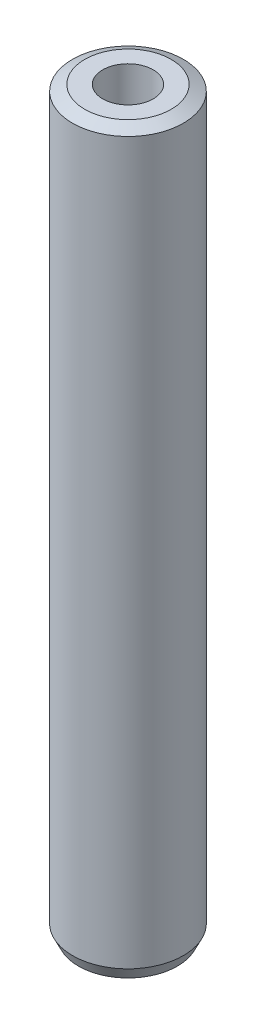
SolidWorks part; units mm, degrees
ref_plane "Front Plane" through (0, 0, 0) normal (0, 0, 1) x (1, 0, 0)
ref_plane "Top Plane" through (0, 0, 0) normal (0, 1, 0) x (1, 0, 0)
ref_plane "Right Plane" through (0, 0, 0) normal (1, 0, 0) x (0, 0, -1)
sketch "Sketch1" plane through (0, 0, 0) normal (0, 1, 0) x (1, 0, 0)
  circle A0 centre (0, 0) radius 45
  dimension "SHAFT_OD" = 90
extrude "Boss-Extrude1" add sketch "Sketch1" along normal blind 600
sketch "Sketch2" plane through (0, 0, 0) normal (0, 1, 0) x (1, 0, 0)
  circle A0 centre (0, 0) radius 20.4917
  dimension "BORE_D" = 40.9834
extrude "Cut-Extrude1" cut sketch "Sketch2" along normal through all
chamfer "Chamfer1" distance 4.8571 angle 63.806 2 edges at (0, 600, 45) (0, 0, 45) first distance on face at (0, 600, 45) first distance on face at (0, 0, 20.4917)
